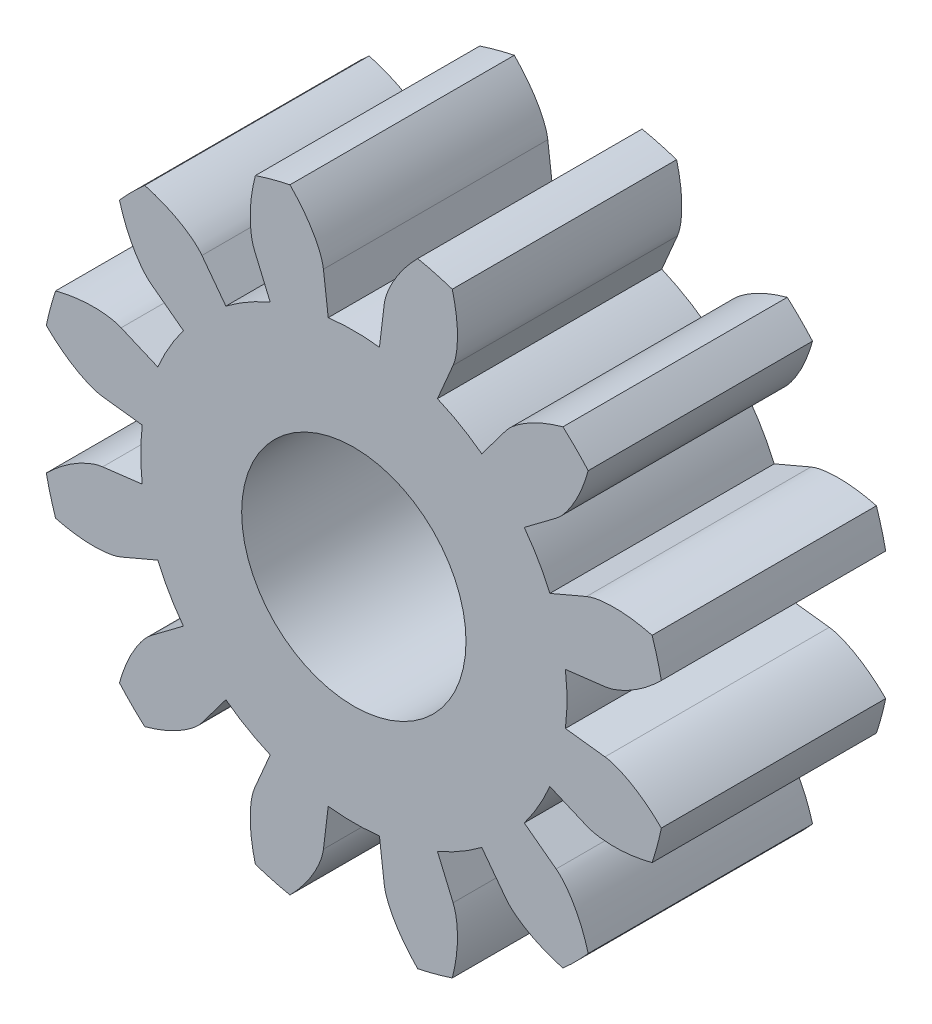
SolidWorks part; units mm, degrees
ref_plane "前视基准面" through (0, 0, 0) normal (0, 0, 1) x (1, 0, 0)
ref_plane "上视基准面" through (0, 0, 0) normal (0, 1, 0) x (1, 0, 0)
ref_plane "右视基准面" through (0, 0, 0) normal (1, 0, 0) x (0, 0, -1)
other "Configuration Table"
sketch "草图1" plane through (0, 0, 0) normal (0, 0, 1) x (1, 0, 0)
  line L0 (0, 0) -> (1.2, 0) construction
  line L1 (0, 0) -> (1.1897, 0.1566) construction
  line L2 (0, 0) -> (1.1195, 0.1354)
  line L3 (1.1897, 0.1566) -> (1.1897, -0.1566) construction
  line L4 (0, 0) -> (1.1195, -0.1354)
  circle A0 centre (0, 0) radius 1.4
  circle A1 centre (0, 0) radius 1.2 construction
  circle A2 centre (0, 0) radius 0.95
  circle A3 centre (0, 0) radius 1.1276 construction
  circle A4 centre (0, 0) radius 0.5
  spline S0 degree 4 poles (1.1195, 0.1354) (1.128, 0.1365) (1.1516, 0.1411) (1.1949, 0.157) (1.2609, 0.1921) (1.3385, 0.2504) (1.4265, 0.3386) (1.513, 0.4563) (1.5884, 0.5979) (1.6479, 0.7602) (1.6868, 0.9286) (1.7064, 1.1002) (1.7082, 1.2814) (1.6868, 1.5048) (1.6275, 1.7661) (1.5147, 2.0566) (1.3415, 2.356) (1.1264, 2.6272) (0.878, 2.867) (0.599, 3.0728) (0.3008, 3.2436) (-0.0211, 3.378) (-0.346, 3.4768) (-0.6967, 3.5387) (-0.9642, 3.5622) (-1.2659, 3.561) (-1.4376, 3.5485) (-1.6326, 3.5286) (-1.737, 3.508) (-1.8243, 3.4941) (-1.8493, 3.4877) (-1.868, 3.4841) knots 0 0 0 0 0 0.005604 0.015718 0.02996 0.048734 0.068727 0.096889 0.125051 0.153212 0.181374 0.209535 0.237696 0.271429 0.327752 0.384075 0.440398 0.496721 0.553044 0.609367 0.66569 0.722013 0.778336 0.834659 0.890982 0.909091 0.954545 0.977273 0.988636 1 1 1 1 1 construction
  spline S1 degree 4 poles (1.1195, 0.1354) (1.128, 0.1365) (1.1516, 0.1411) (1.1949, 0.157) (1.2609, 0.1921) (1.3385, 0.2504) (1.4265, 0.3386) (1.513, 0.4563) (1.5884, 0.5979) (1.6479, 0.7602) (1.6868, 0.9286) (1.7064, 1.1002) (1.7082, 1.2814) (1.6868, 1.5048) (1.6275, 1.7661) (1.5147, 2.0566) (1.3415, 2.356) (1.1264, 2.6272) (0.878, 2.867) (0.599, 3.0728) (0.3008, 3.2436) (-0.0211, 3.378) (-0.346, 3.4768) (-0.6967, 3.5387) (-0.9642, 3.5622) (-1.1881, 3.5613) (-1.292, 3.5571) (-1.3172, 3.5557) knots 0 0 0 0 0 0.005604 0.015718 0.02996 0.048734 0.068727 0.096889 0.125051 0.153212 0.181374 0.209535 0.237696 0.271429 0.327752 0.384075 0.440398 0.496721 0.553044 0.609367 0.66569 0.722013 0.778336 0.834659 0.890982 0.909091 0.909091 0.909091 0.909091 0.909091
  spline S2 degree 4 poles (1.1195, -0.1354) (1.128, -0.1365) (1.1516, -0.1411) (1.1949, -0.157) (1.2609, -0.1921) (1.3385, -0.2504) (1.4265, -0.3386) (1.513, -0.4563) (1.5884, -0.5979) (1.6479, -0.7602) (1.6868, -0.9286) (1.7064, -1.1002) (1.7082, -1.2814) (1.6868, -1.5048) (1.6275, -1.7661) (1.5147, -2.0566) (1.3415, -2.356) (1.1264, -2.6272) (0.878, -2.867) (0.599, -3.0728) (0.3008, -3.2436) (-0.0211, -3.378) (-0.346, -3.4768) (-0.6967, -3.5387) (-0.9642, -3.5622) (-1.2659, -3.561) (-1.4376, -3.5485) (-1.6326, -3.5286) (-1.737, -3.508) (-1.8243, -3.4941) (-1.8493, -3.4877) (-1.868, -3.4841) knots 0 0 0 0 0 0.005604 0.015718 0.02996 0.048734 0.068727 0.096889 0.125051 0.153212 0.181374 0.209535 0.237696 0.271429 0.327752 0.384075 0.440398 0.496721 0.553044 0.609367 0.66569 0.722013 0.778336 0.834659 0.890982 0.909091 0.954545 0.977273 0.988636 1 1 1 1 1 construction
  spline S3 degree 4 poles (1.1195, -0.1354) (1.128, -0.1365) (1.1516, -0.1411) (1.1949, -0.157) (1.2609, -0.1921) (1.3385, -0.2504) (1.4265, -0.3386) (1.513, -0.4563) (1.5884, -0.5979) (1.6479, -0.7602) (1.6868, -0.9286) (1.7064, -1.1002) (1.7082, -1.2814) (1.6868, -1.5048) (1.6275, -1.7661) (1.5147, -2.0566) (1.3415, -2.356) (1.1264, -2.6272) (0.878, -2.867) (0.599, -3.0728) (0.3008, -3.2436) (-0.0211, -3.378) (-0.346, -3.4768) (-0.6967, -3.5387) (-0.9642, -3.5622) (-1.1881, -3.5613) (-1.292, -3.5571) (-1.3172, -3.5557) knots 0 0 0 0 0 0.005604 0.015718 0.02996 0.048734 0.068727 0.096889 0.125051 0.153212 0.181374 0.209535 0.237696 0.271429 0.327752 0.384075 0.440398 0.496721 0.553044 0.609367 0.66569 0.722013 0.778336 0.834659 0.890982 0.909091 0.909091 0.909091 0.909091 0.909091
  point P15 (1.1897, 0)
  dimension "齿顶圆直径" = 2.8
  dimension "分度圆直径" = 2.4
  dimension "齿根圆直径" = 1.9
  dimension "基圆直径" = 2.2553
  dimension "内孔直径" = 1
  dimension "渐近线镜像线夹角" = 7.5
extrude "凸台-拉伸1" add sketch "草图1" along normal blind 1 contours A0 | A4
extrude "切除-拉伸1" cut sketch "草图1<3>" along normal through all contours A2 S3 A0 S1 region at (1.2063, 0, 0)
sketch "草图1<3>" plane through (0, 0, 0) normal (0, 0, 1) x (1, 0, 0) same geometry as "草图1"
pattern_circular "阵列(圆周)1" count 12 every 30 about axis through (0, 0, 1) along (0, 0, 1) of "切除-拉伸1"
equation "\"m\" = 0.2'模数"
equation "\"z\" = 12'齿数"
equation "\"a\"= 20度'压力角"
equation "\"d\"= \"m\" * \"z\"'分度圆直径"
equation "\"da\"= ( \"z\" + 2 ) * \"m\"'齿顶圆直径"
equation "\"df\"= ( \"z\" - 2.5 ) * \"m\"'齿根圆直径"
equation "\"s\"= 0.5 * PI * \"m\"'分度圆齿厚"
equation "\"r\"= 0.38 * \"m\"'齿根圆角"
equation "\"B\"= 0.3 * \"d\"'齿厚"
equation "\"db\"= \"m\" * \"z\" * cos ( \"a\" )'基圆直径"
equation "\"rb\"= \"db\" / 2'基圆半径"
equation "\"齿顶圆直径@草图1\"= \"da\""
equation "\"分度圆直径@草图1\"= \"d\""
equation "\"齿根圆直径@草图1\"= \"df\""
equation "\"基圆直径@草图1\"= \"db\""
equation "\"渐近线镜像线夹角@草图1\"= 360 / 4 / \"z\""
equation "\"h\" = 1'齿轮厚度"
equation "\"ir\"= 1'内孔直径"
equation "\"内孔直径@草图1\"= \"ir\""
equation "\"齿轮厚@凸台-拉伸1\"= \"h\""
equation "\"齿轮夹角@阵列(圆周)1\"= 360 / \"z\""
equation "\"齿数@阵列(圆周)1\"= \"z\""
